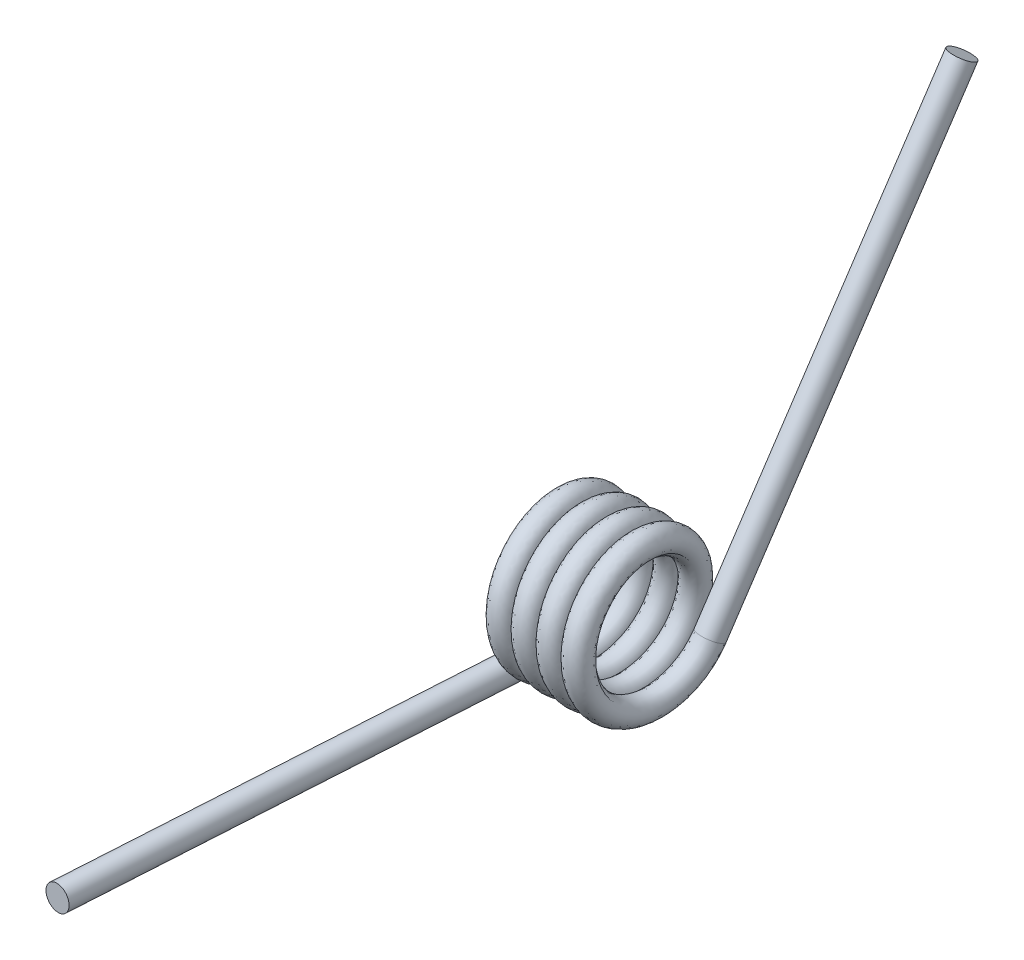
SolidWorks part; units mm, degrees
material "AISI 1045 Steel, cold drawn"
ref_plane "Front" through (0, 0, 0) normal (0, 0, 1) x (1, 0, 0)
ref_plane "Top" through (0, 0, 0) normal (0, 1, 0) x (1, 0, 0)
ref_plane "Right" through (0, 0, 0) normal (1, 0, 0) x (0, 0, -1)
sketch "Sketch1" plane through (0, 0, 0) normal (1, 0, 0) x (0, 0, -1)
  line L0 (0, 0) -> (0, -4.572) construction
  line L1 (0, -4.572) -> (0, -5.6515) construction
  line L2 (0, -5.6515) -> (0, -6.731) construction
  line L3 (0, 6.731) -> (0, -6.731) construction
  circle A0 centre (0, 0) radius 4.572 construction
  circle A1 centre (0, 0) radius 6.731 construction
  circle A2 centre (0, 0) radius 5.6515
  circle A3 centre (0, -5.6515) radius 1.0795 construction
  circle A4 centre (0, 0) radius 4.3561 construction
curve "Helix/Spiral1" pitch 2.1844 height 9.1089 radius 5.6515 centre (0, 0, 0) axis (1, 0, 0) start towards (0, 0, -1)
ref_plane "Plane1" through (0, -5.6515, 0) normal (0.0614, 0, -0.9981) x (0.9942, 0.0889, 0.0612)
sketch "Sketch2" plane through (0, -5.6515, 0) normal (0.0614, 0, -0.9981) x (0.9942, 0.0889, 0.0612)
  circle A0 centre (0, 0) radius 1.0795
  dimension "D1" = 2.159
sweep "Sweep1" add profiles "Sketch2" path "Helix/Spiral1"
sketch "Sketch3" plane through (0, 0, 0) normal (-0.0614, 0, 0.9981) x (-0.9942, -0.0889, -0.0612)
  circle A1 centre (0.5024, 5.6291) radius 1.0795
  circle A2 centre (0.5024, 5.6291) radius 1.0795
  dimension "D1" = 0
extrude "Extrude1" add sketch "Sketch3" along normal blind 40.64
sketch "Sketch4" plane through (0.0343, 0.4892, -0.2689) normal (0.0614, 0.8747, -0.4808) x (0.9918, -0.1078, -0.0694)
  circle A1 centre (9.6708, 4.5907) radius 1.0795
  circle A2 centre (9.6708, 4.5907) radius 1.0795
  dimension "D1" = 0
extrude "Extrude2" add sketch "Sketch4" along normal blind 40.64
sketch "Sketch5" plane through (0, 0, 0) normal (1, 0, 0) x (0, 0, -1)
  line L0 (-40.5633, -4.572) -> (-40.5633, -6.731) construction
  circle A0 centre (0, 0) radius 4.3561 construction
  circle A1 centre (0, 0) radius 4.3561
equation "\"D4@Helix/Spiral1\"=\"Wire Dia@Sketch1\"+.001"
equation "\"D1@Sketch2\"=\"Wire Dia@Sketch1\""
equation "\"D1@Extrude2\"=\"Leg Length@Extrude1\""
